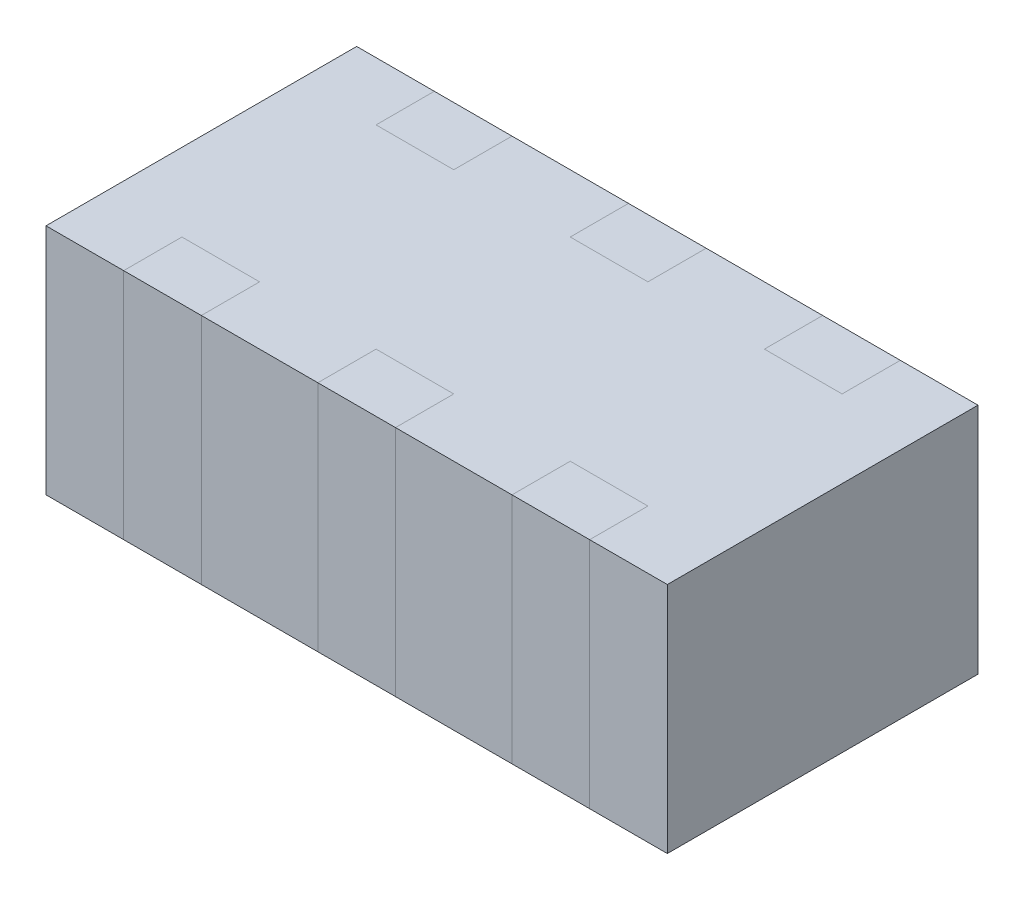
SolidWorks part; units mm, degrees
note: The reader was unsure of these and kept them because the rebuilt part matched: shared geometry of "Sketch2<2>".
ref_plane "Front Plane" through (0, 0, 0) normal (0, 0, 1) x (1, 0, 0)
ref_plane "Top Plane" through (0, 0, 0) normal (0, 1, 0) x (1, 0, 0)
ref_plane "Right Plane" through (0, 0, 0) normal (1, 0, 0) x (0, 0, -1)
sketch "Sketch1" plane through (0, 0, 0) normal (0, 1, 0) x (1, 0, 0)
  line L1 (-0.8, 0.4) -> (0.8, 0.4)
  line L2 (-0.8, 0.4) -> (-0.8, -0.4)
  line L3 (-0.8, -0.4) -> (0.8, -0.4)
  line L4 (0.8, 0.4) -> (0.8, -0.4)
  line L5 (-0.8, 0.4) -> (0.8, -0.4) construction
  line L6 (-0.8, -0.4) -> (0.8, 0.4) construction
  point P0 (0, 0)
  dimension "D1" = 0.8
  dimension "D2" = 1.6
extrude "Boss-Extrude1" add sketch "Sketch1" along normal blind 0.6
sketch "Sketch2" plane through (0, 0.6, 0) normal (0, 1, 0) x (1, 0, 0)
  line L0 (-0.8, -0.4) -> (0.8, -0.4) construction
  line L1 (-0.6, -0.4) -> (-0.4, -0.4)
  line L2 (-0.6, -0.4) -> (-0.6, -0.25)
  line L3 (-0.6, -0.25) -> (-0.4, -0.25)
  line L4 (-0.4, -0.4) -> (-0.4, -0.25)
  line L5 (0.8, -0.4) -> (0.8, 0.4) construction
  line L6 (0.4, -0.4) -> (0.6, -0.4)
  line L7 (0.4, -0.4) -> (0.4, -0.25)
  line L8 (0.4, -0.25) -> (0.6, -0.25)
  line L9 (0.6, -0.4) -> (0.6, -0.25)
  line L11 (-0.1, -0.4) -> (0.1, -0.4)
  line L12 (-0.1, -0.4) -> (-0.1, -0.25)
  line L13 (-0.1, -0.25) -> (0.1, -0.25)
  line L14 (0.1, -0.4) -> (0.1, -0.25)
  point P16 (0.5, -0.25)
  point P17 (0, -0.25)
  dimension "D1" = 0.2
  dimension "D2" = 0.15
  dimension "D3" = 0.15
  dimension "D4" = 0.2
  dimension "D5" = 0.2
  dimension "D6" = 0.15
  dimension "D7" = 0.2
  dimension "D8" = 0.5
  dimension "D9" = 0.3
extrude "Cut-Extrude1" cut sketch "Sketch2" against normal blind 0.6
mirror "Mirror1" about plane through (0, 0, 0) normal (0, 0, 1) of "Cut-Extrude1"
extrude "Boss-Extrude2" add sketch "Sketch2<2>" against normal blind 0.6 separate body contours L6 L9 L8 L7
sketch "Sketch2<2>" plane through (0, 0.6, 0) normal (0, 1, 0) x (1, 0, 0) same geometry as "Sketch2"
mirror "Mirror3" about plane through (0, 0, 0) normal (0, 0, 1) of bodies 104 106 105
